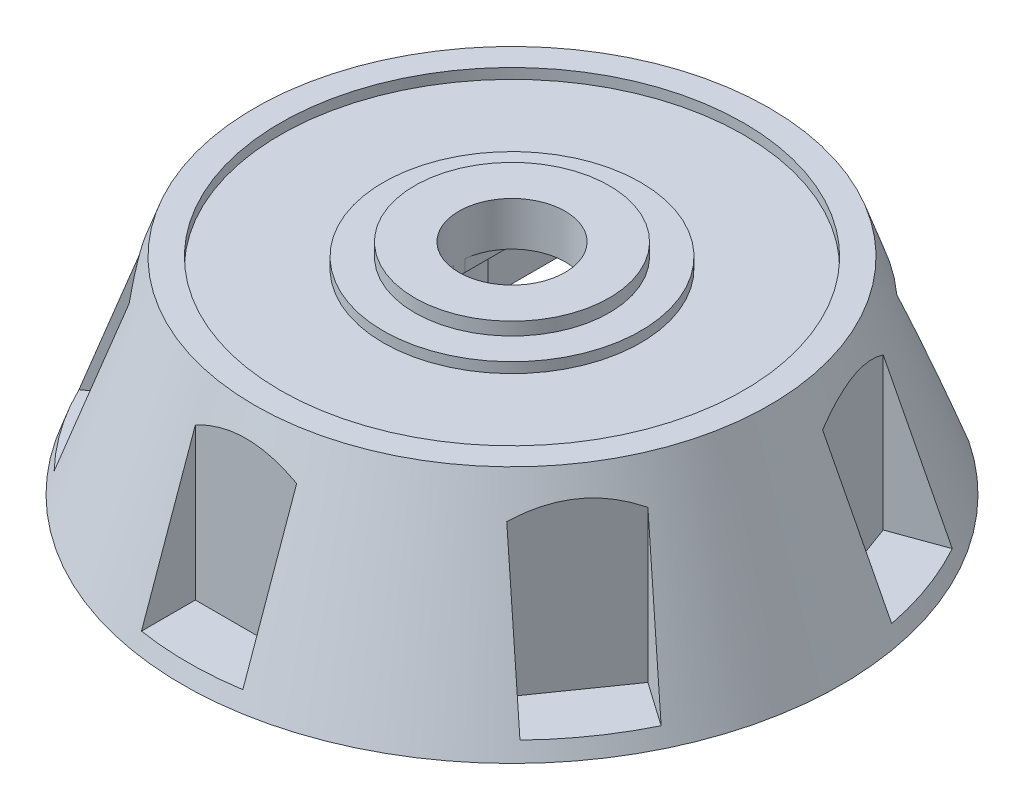
SolidWorks part; units mm, degrees
ref_plane "Front Plane" through (0, 0, 0) normal (0, 0, 1) x (1, 0, 0)
ref_plane "Top Plane" through (0, 0, 0) normal (0, 1, 0) x (1, 0, 0)
ref_plane "Right Plane" through (0, 0, 0) normal (1, 0, 0) x (0, 0, -1)
sketch "Sketch3" plane through (0, 0, 0) normal (0, 0, 1) x (1, 0, 0)
  line L0 (60.96, 0) -> (81.28, 0)
  line L1 (0, 0) -> (60.96, 0)
  line L2 (0, 0) -> (0, 50.8)
  line L3 (0, 50.8) -> (63.5, 50.8)
  line L5 (63.5, 50.8) -> (81.28, 0)
  dimension "D1" = 50.8
  dimension "D2" = 63.5
  dimension "D3" = 53.8216
  dimension "D4" = 60.96
  dimension "D5" = 20.32
revolve "Revolve1" add sketch "Sketch3" angle 360 about L2
sketch "Sketch4" plane through (0, 0, 0) normal (0, -1, 0) x (-1, 0, 0)
  line L8 (-45, 39.0789) -> (-45, 81.5407)
  line L9 (-45, 81.5407) -> (45, 81.5407)
  line L10 (45, 39.0789) -> (45, 81.5407)
  arc A0 (-45, 39.0789) -> (45, 39.0789) centre (0, 0) ccw
  circle A1 centre (0, 0) radius 81.28 construction
  dimension "D1" = 59.6
  dimension "D2" = 45
  dimension "D3" = 81.5407
extrude "Cut-Extrude1" cut sketch "Sketch4" against normal blind 40.2 contours L10 L9 L8 A0
sketch "Sketch5" plane through (0, 50.8, 0) normal (0, 1, 0) x (1, 0, 0)
  circle A0 centre (0, 0) radius 13.1
  circle A1 centre (0, 0) radius 24
  circle A2 centre (0, 0) radius 63.5 construction
  dimension "D1" = 26.2
  dimension "D2" = 48
extrude "Cut-Extrude2" cut sketch "Sketch5" along direction (0, -1, 0) on the side against the normal up to next (10.6 mm away) contours A0
extrude "Boss-Extrude1" add sketch "Sketch5<3>" along normal blind 3.175
sketch "Sketch5<3>" plane through (0, 50.8, 0) normal (0, 1, 0) x (1, 0, 0) same geometry as "Sketch5"
sketch "Sketch6" plane through (0, 50.8, 0) normal (0, 1, 0) x (1, 0, 0)
  line L0 (0, 0) -> (0, -80) construction
  line L2 (12.5, -65.6081) -> (-12.5, -65.6081)
  line L3 (12.5, -65.6081) -> (12.5, -94.3919)
  line L4 (12.5, -94.3919) -> (-12.5, -94.3919)
  line L5 (-12.5, -65.6081) -> (-12.5, -94.3919)
  circle A0 centre (0, 0) radius 63.5 construction
  dimension "D1" = 12.5
  dimension "D2" = 12.5
  dimension "D3" = 65.6081
  dimension "D4" = 94.3919
extrude "Cut-Extrude3" cut sketch "Sketch6" against normal offset from surface (46.8 mm away) 4 contours L4 L5 L2 L3 up to face at (0, 0, 8.5287)
pattern_circular "CirPattern1" count 3 every 55 about axis through (0, 0, 0) along (0, 1, 0) of "Cut-Extrude3" reverse direction yes
pattern_circular "CirPattern2" count 3 every 55 about axis through (0, 0, 0) along (0, 1, 0) of "Cut-Extrude3"
sketch "Sketch7" plane through (0, 40.2, 0) normal (0, -1, 0) x (1, 0, 0)
  line L4 (0, -33) -> (0, 23.8422) construction
  line L5 (12.2, -4.5789) -> (-12.2, -4.5789) construction
  line L6 (45, -39.0789) -> (45, -49.9218) construction
  line L7 (13.0268, 18.6285) -> (-13.0268, 18.6285)
  line L8 (13.0268, 18.6285) -> (13.0268, -27.7863)
  line L9 (13.0268, -27.7863) -> (-13.0268, -27.7863)
  line L10 (-13.0268, 18.6285) -> (-13.0268, -27.7863)
  line L11 (13.0268, 18.6285) -> (-13.0268, -27.7863) construction
  line L12 (13.0268, -27.7863) -> (-13.0268, 18.6285) construction
  point P4 (0, -4.5789)
  dimension "D1" = 31.9732
  dimension "D2" = 45
  dimension "D3" = 11.2926
  dimension "D4" = 34.5
extrude "Cut-Extrude4" cut sketch "Sketch7" against normal blind 2.95
sketch "Sketch8" plane through (0, 40.2, 0) normal (0, -1, 0) x (1, 0, 0)
  circle A0 centre (15, -12.5) radius 1.4
  circle A1 centre (15, -29.5) radius 1.4
  circle A2 centre (8.5, -35.8) radius 1.4
  circle A3 centre (-8.5, -35.8) radius 1.4
  circle A4 centre (-15, -29.5) radius 1.4
  circle A5 centre (-15, -12.5) radius 1.4
  circle A6 centre (-15, 4.5) radius 1.4
  circle A7 centre (15, 4.5) radius 1.4
hole_wizard "M2.5 Clearance Hole1" positions "Sketch9" profile "Sketch10" hole size "M2.5" standard "ANSI Metric"
sketch "Sketch9" plane through (0, 40.2, 0) normal (0, -1, 0) x (-1, 0, 0)
  point P0 (-15, -4.5)
  point P3 (15, -4.5)
  point P6 (15, 12.5)
  point P9 (-15, 12.5)
  point P12 (15, 29.5)
  point P15 (-15, 29.5)
  point P18 (-8.5, 35.8)
  point P21 (8.5, 35.8)
sketch "Sketch10" plane through (15, 40.2, 4.5) normal (1, 0, 0) x (0, 0, -1)
  line L0 (0, 0) -> (0, 6.8712)
  line L1 (0, 6.8712) -> (1.45, 6)
  line L2 (1.45, 6) -> (1.45, 0)
  line L5 (1.45, 0) -> (0, 0)
  line L10 (0, 6.8712) -> (-1.45, 6) construction
  line L11 (0, -6.35) -> (0, 107.95) construction
  dimension "Hole Dia." = 2.9
  dimension "Hole Depth" = 6
  dimension "Drill Angle" = 118
sketch "Sketch11" plane through (0, 50.8, 0) normal (0, 1, 0) x (1, 0, 0)
  circle A0 centre (0, 0) radius 31.75
  circle A1 centre (0, 0) radius 57.15
  dimension "D1" = 25.4
  dimension "D2" = 63.5
extrude "Cut-Extrude5" cut sketch "Sketch11" against normal blind 2.54
